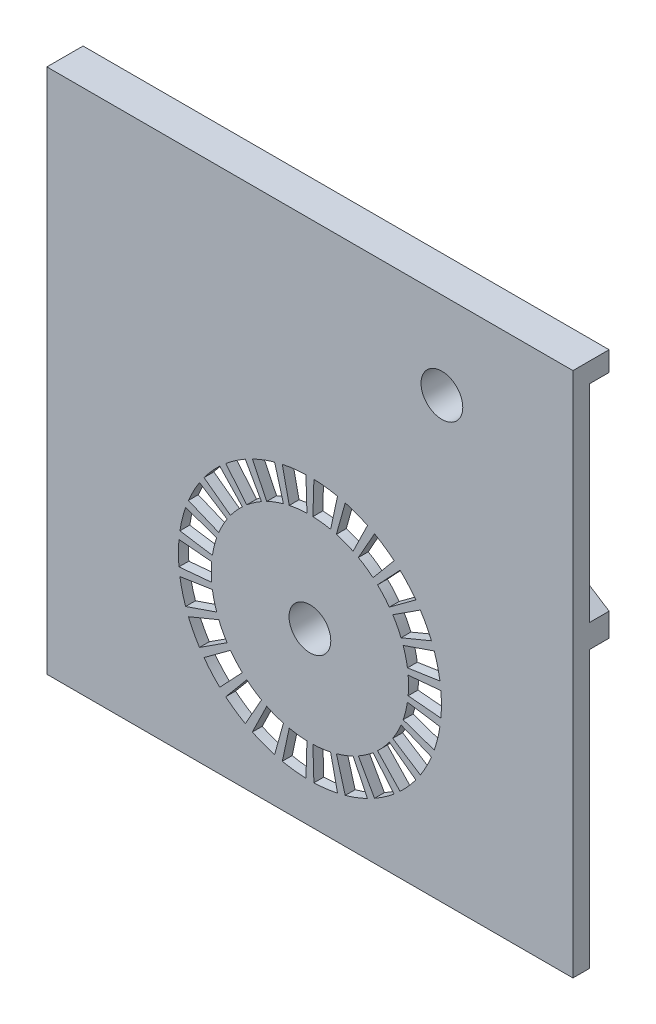
SolidWorks part; units mm, degrees
ref_plane "Front Plane" through (0, 0, 0) normal (0, 0, 1) x (1, 0, 0)
ref_plane "Top Plane" through (0, 0, 0) normal (0, 1, 0) x (1, 0, 0)
ref_plane "Right Plane" through (0, 0, 0) normal (1, 0, 0) x (0, 0, -1)
sketch "LED panel" plane through (0, 0, 0) normal (0, 0, 1) x (1, 0, 0)
  line L1 (-40, 40) -> (40, 40)
  line L2 (-40, 40) -> (-40, -40)
  line L3 (-40, -40) -> (40, -40)
  line L4 (40, 40) -> (40, -40)
  line L5 (-40, 40) -> (40, -40) construction
  line L6 (-40, -40) -> (40, 40) construction
  point P0 (0, 0)
  dimension "D1" = 80
  dimension "D2" = 80
extrude "Extrude LED panel" add sketch "LED panel" along normal blind 2.5
sketch "Sketch3" plane through (0, 0, 2.5) normal (0, 0, 1) x (1, 0, 0)
  circle A0 centre (0, -14) radius 5.9987
  circle A1 centre (20.0721, 26.7806) radius 6.0029
extrude "Boss-Extrude2" add sketch "Sketch3" against normal blind 7
sketch "Sketch1" plane through (0, 0, 2.5) normal (0, 0, 1) x (1, 0, 0)
  line L0 (-40, -14) -> (40, -14) construction
  line L3 (0, 40) -> (0, -40) construction
  line L4 (40, 40) -> (-40, 40) construction
  line L5 (-40, -40) -> (40, -40) construction
  line L6 (0, -14) -> (52.2337, -7.6577) construction
  line L7 (0, -14) -> (47.0949, -19.7184) construction
  line L8 (0, -14) -> (19.9179, -12.19) construction
  line L9 (0, -14) -> (41.9979, -17.8164) construction
  line L10 (14.9384, -12.6425) -> (19.9179, -12.19)
  line L11 (14.9384, -15.3575) -> (19.9179, -15.81)
  line L12 (14.8292, -16.257) -> (19.7723, -17.0093)
  line L13 (14.1795, -18.893) -> (18.906, -20.5241)
  line L14 (13.8582, -19.7403) -> (18.4776, -21.6537)
  line L15 (12.5965, -22.1442) -> (16.7953, -24.859)
  line L16 (12.0818, -22.8899) -> (16.109, -25.8532)
  line L17 (10.2814, -24.9221) -> (13.7085, -28.5628)
  line L18 (9.6032, -25.523) -> (12.8043, -29.364)
  line L19 (7.3688, -27.0652) -> (9.8251, -31.4203)
  line L20 (6.5665, -27.4863) -> (8.7554, -31.9818)
  line L21 (4.028, -28.4491) -> (5.3706, -33.2654)
  line L22 (3.1482, -28.6659) -> (4.1976, -33.5545)
  line L23 (0.453, -28.9932) -> (0.6041, -33.9909)
  line L24 (-0.453, -28.9932) -> (-0.6041, -33.9909)
  line L25 (-3.1482, -28.6659) -> (-4.1976, -33.5545)
  line L26 (-4.028, -28.4491) -> (-5.3706, -33.2654)
  line L27 (-6.5665, -27.4863) -> (-8.7554, -31.9818)
  line L28 (-7.3688, -27.0652) -> (-9.8251, -31.4203)
  line L29 (-9.6032, -25.523) -> (-12.8043, -29.364)
  line L30 (-10.2814, -24.9221) -> (-13.7085, -28.5628)
  line L31 (-12.0818, -22.8899) -> (-16.109, -25.8532)
  line L32 (-12.5965, -22.1442) -> (-16.7953, -24.859)
  line L33 (-13.8582, -19.7403) -> (-18.4776, -21.6537)
  line L34 (-14.1795, -18.893) -> (-18.906, -20.5241)
  line L35 (-14.8292, -16.257) -> (-19.7723, -17.0093)
  line L36 (-14.9384, -15.3575) -> (-19.9179, -15.81)
  line L37 (-14.9384, -12.6425) -> (-19.9179, -12.19)
  line L38 (-14.8292, -11.743) -> (-19.7723, -10.9907)
  line L39 (-14.1795, -9.107) -> (-18.906, -7.4759)
  line L40 (-13.8582, -8.2597) -> (-18.4776, -6.3463)
  line L41 (-12.5965, -5.8558) -> (-16.7953, -3.141)
  line L42 (-12.0818, -5.1101) -> (-16.109, -2.1468)
  line L43 (-10.2814, -3.0779) -> (-13.7085, 0.5628)
  line L44 (-9.6032, -2.477) -> (-12.8043, 1.364)
  line L45 (-7.3688, -0.9348) -> (-9.8251, 3.4203)
  line L46 (-6.5665, -0.5137) -> (-8.7554, 3.9818)
  line L47 (-4.028, 0.4491) -> (-5.3706, 5.2654)
  line L48 (-3.1482, 0.6659) -> (-4.1976, 5.5545)
  line L49 (-0.453, 0.9932) -> (-0.6041, 5.9909)
  line L50 (0.453, 0.9932) -> (0.6041, 5.9909)
  line L51 (3.1482, 0.6659) -> (4.1976, 5.5545)
  line L52 (4.028, 0.4491) -> (5.3706, 5.2654)
  line L53 (6.5665, -0.5137) -> (8.7554, 3.9818)
  line L54 (7.3688, -0.9348) -> (9.8251, 3.4203)
  line L55 (9.6032, -2.477) -> (12.8043, 1.364)
  line L56 (10.2814, -3.0779) -> (13.7085, 0.5628)
  line L57 (12.0818, -5.1101) -> (16.109, -2.1468)
  line L58 (12.5965, -5.8558) -> (16.7953, -3.141)
  line L59 (13.8582, -8.2597) -> (18.4776, -6.3463)
  line L60 (14.1795, -9.107) -> (18.906, -7.4759)
  line L61 (14.8292, -11.743) -> (19.7723, -10.9907)
  line L62 (-40, -40) -> (40, -40) construction
  line L63 (40, -40) -> (40, 40) construction
  line L64 (-40, 40) -> (-40, -40) construction
  arc A0 (19.9179, -15.81) -> (19.9179, -12.19) centre (0, -14) ccw
  arc A1 (14.9384, -15.3575) -> (14.9384, -12.6425) centre (0, -14) ccw
  arc A2 (18.906, -20.5241) -> (19.7723, -17.0093) centre (0, -14) ccw
  arc A3 (14.1795, -18.893) -> (14.8292, -16.257) centre (0, -14) ccw
  arc A4 (16.7953, -24.859) -> (18.4776, -21.6537) centre (0, -14) ccw
  arc A5 (12.5965, -22.1442) -> (13.8582, -19.7403) centre (0, -14) ccw
  arc A6 (13.7085, -28.5628) -> (16.109, -25.8532) centre (0, -14) ccw
  arc A7 (10.2814, -24.9221) -> (12.0818, -22.8899) centre (0, -14) ccw
  arc A8 (9.8251, -31.4203) -> (12.8043, -29.364) centre (0, -14) ccw
  arc A9 (7.3688, -27.0652) -> (9.6032, -25.523) centre (0, -14) ccw
  arc A10 (5.3706, -33.2654) -> (8.7554, -31.9818) centre (0, -14) ccw
  arc A11 (4.028, -28.4491) -> (6.5665, -27.4863) centre (0, -14) ccw
  arc A12 (0.6041, -33.9909) -> (4.1976, -33.5545) centre (0, -14) ccw
  arc A13 (0.453, -28.9932) -> (3.1482, -28.6659) centre (0, -14) ccw
  arc A14 (-4.1976, -33.5545) -> (-0.6041, -33.9909) centre (0, -14) ccw
  arc A15 (-3.1482, -28.6659) -> (-0.453, -28.9932) centre (0, -14) ccw
  arc A16 (-8.7554, -31.9818) -> (-5.3706, -33.2654) centre (0, -14) ccw
  arc A17 (-6.5665, -27.4863) -> (-4.028, -28.4491) centre (0, -14) ccw
  arc A18 (-12.8043, -29.364) -> (-9.8251, -31.4203) centre (0, -14) ccw
  arc A19 (-9.6032, -25.523) -> (-7.3688, -27.0652) centre (0, -14) ccw
  arc A20 (-16.109, -25.8532) -> (-13.7085, -28.5628) centre (0, -14) ccw
  arc A21 (-12.0818, -22.8899) -> (-10.2814, -24.9221) centre (0, -14) ccw
  arc A22 (-18.4776, -21.6537) -> (-16.7953, -24.859) centre (0, -14) ccw
  arc A23 (-13.8582, -19.7403) -> (-12.5965, -22.1442) centre (0, -14) ccw
  arc A24 (-19.7723, -17.0093) -> (-18.906, -20.5241) centre (0, -14) ccw
  arc A25 (-14.8292, -16.257) -> (-14.1795, -18.893) centre (0, -14) ccw
  arc A26 (-19.9179, -12.19) -> (-19.9179, -15.81) centre (0, -14) ccw
  arc A27 (-14.9384, -12.6425) -> (-14.9384, -15.3575) centre (0, -14) ccw
  arc A28 (-18.906, -7.4759) -> (-19.7723, -10.9907) centre (0, -14) ccw
  arc A29 (-14.1795, -9.107) -> (-14.8292, -11.743) centre (0, -14) ccw
  arc A30 (-16.7953, -3.141) -> (-18.4776, -6.3463) centre (0, -14) ccw
  arc A31 (-12.5965, -5.8558) -> (-13.8582, -8.2597) centre (0, -14) ccw
  arc A32 (-13.7085, 0.5628) -> (-16.109, -2.1468) centre (0, -14) ccw
  arc A33 (-10.2814, -3.0779) -> (-12.0818, -5.1101) centre (0, -14) ccw
  arc A34 (-9.8251, 3.4203) -> (-12.8043, 1.364) centre (0, -14) ccw
  arc A35 (-7.3688, -0.9348) -> (-9.6032, -2.477) centre (0, -14) ccw
  arc A36 (-5.3706, 5.2654) -> (-8.7554, 3.9818) centre (0, -14) ccw
  arc A37 (-4.028, 0.4491) -> (-6.5665, -0.5137) centre (0, -14) ccw
  arc A38 (-0.6041, 5.9909) -> (-4.1976, 5.5545) centre (0, -14) ccw
  arc A39 (-0.453, 0.9932) -> (-3.1482, 0.6659) centre (0, -14) ccw
  arc A40 (4.1976, 5.5545) -> (0.6041, 5.9909) centre (0, -14) ccw
  arc A41 (3.1482, 0.6659) -> (0.453, 0.9932) centre (0, -14) ccw
  arc A42 (8.7554, 3.9818) -> (5.3706, 5.2654) centre (0, -14) ccw
  arc A43 (6.5665, -0.5137) -> (4.028, 0.4491) centre (0, -14) ccw
  arc A44 (12.8043, 1.364) -> (9.8251, 3.4203) centre (0, -14) ccw
  arc A45 (9.6032, -2.477) -> (7.3688, -0.9348) centre (0, -14) ccw
  arc A46 (16.109, -2.1468) -> (13.7085, 0.5628) centre (0, -14) ccw
  arc A47 (12.0818, -5.1101) -> (10.2814, -3.0779) centre (0, -14) ccw
  arc A48 (18.4776, -6.3463) -> (16.7953, -3.141) centre (0, -14) ccw
  arc A49 (13.8582, -8.2597) -> (12.5965, -5.8558) centre (0, -14) ccw
  arc A50 (19.7723, -10.9907) -> (18.906, -7.4759) centre (0, -14) ccw
  arc A51 (14.8292, -11.743) -> (14.1795, -9.107) centre (0, -14) ccw
  circle A52 centre (0, -14) radius 3.175
  point P124 (0, -14)
  dimension "D2" = 40
  dimension "D4" = 5
  dimension "D9" = 6.35
  dimension "D1" = 6.923
  dimension "D3" = 6.923
  dimension "D5" = 5.192
  dimension "D6" = 5.192
  dimension "D8" = 26
  dimension "D7" = 26
extrude "Cut arrow indication holes" cut sketch "Sketch1" against normal through all
sketch "Sketch4" plane through (0, 0, 0) normal (0, 0, 1) x (1, 0, 0)
  circle A0 centre (20.0721, 26.7806) radius 3.175
  dimension "D1" = 6.35
  dimension "D2" = 20.0721
  dimension "D3" = 26.7806
extrude "Cut hole for secondary rod" cut sketch "Sketch4" along normal through all and the other way blind 7
sketch "Sketch2" plane through (0, 0, 0) normal (0, 0, -1) x (-1, 0, 0)
  line L0 (-1, 13.4818) -> (-1, 14.9818)
  line L1 (-1, 14.9818) -> (1, 14.9818)
  line L2 (1, 14.9818) -> (1, 13.4818)
  line L3 (0, -14) -> (0, 30.4199) construction
  line L4 (-8.9582, -40) -> (8.9582, -40)
  line L5 (40, -40) -> (-40, -40) construction
  arc A0 (-1, 13.4818) -> (-8.9582, -40) centre (0, -14) ccw
  arc A1 (8.9582, -40) -> (1, 13.4818) centre (0, -14) ccw
  circle A2 centre (0, -14) radius 5.9987
  point P5 (0, 14.9818)
  dimension "D1" = 55
  dimension "D2" = 2
  dimension "D3" = 1.5
extrude "Cut slot for PCB" cut sketch "Sketch2" against normal blind 1
sketch "Sketch6" plane through (0, 0, 0) normal (0, 0, -1) x (-1, 0, 0)
  line L0 (40, 40) -> (40, -40) construction
  line L1 (-40, 40) -> (40, 40)
  line L2 (-40, 40) -> (-40, 37)
  line L3 (-40, 37) -> (8.9219, 37)
  line L4 (40, 40) -> (40, 37)
  line L6 (8.9219, 37) -> (-40, 5.5647)
  line L7 (-40, -40) -> (-40, 40) construction
  line L8 (14.4714, 37) -> (-40, 1.9987)
  line L10 (14.4714, 37) -> (40, 37)
  line L11 (-40, 5.5647) -> (-40, 1.9987)
  dimension "D1" = 3
  dimension "D2" = 3
extrude "Boss-Extrude3" add sketch "Sketch6" along normal blind 3
equation "\"D6@Sketch1\"=3/4*360/2/26"
